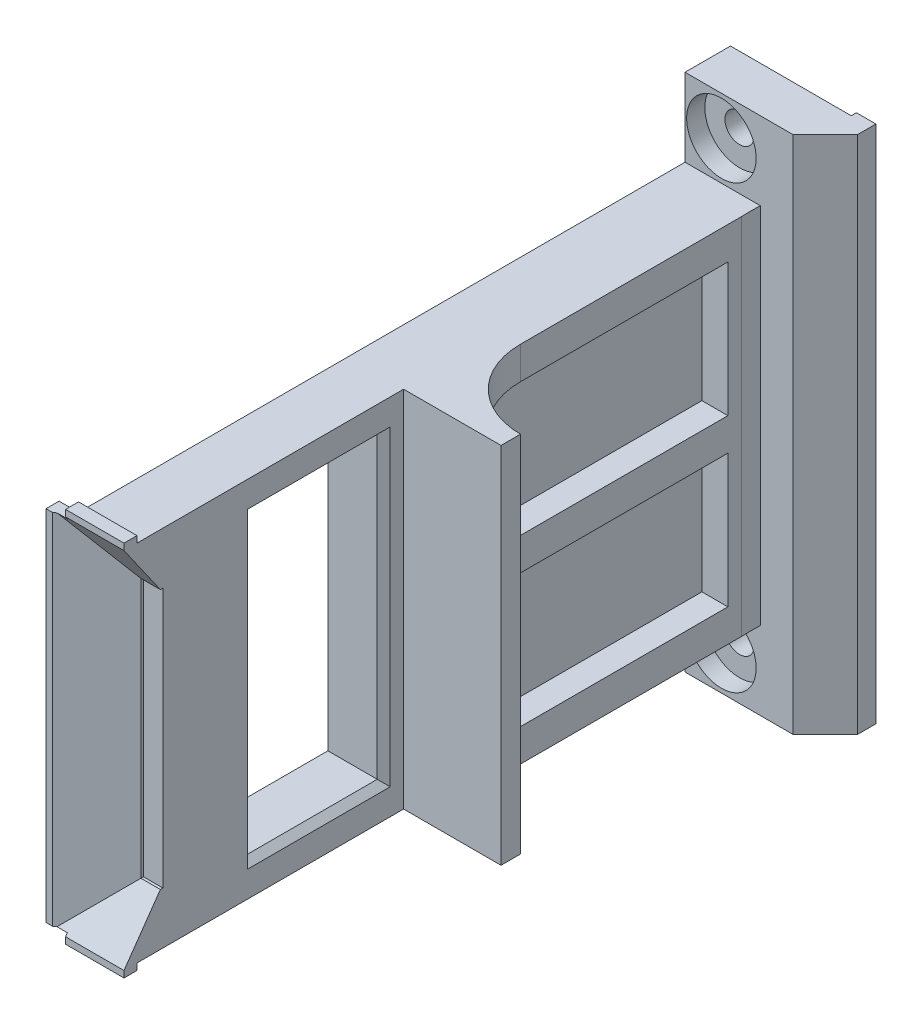
SolidWorks part; units mm, degrees
material "PLA"
ref_plane "정면" through (0, 0, 0) normal (0, 0, 1) x (1, 0, 0)
ref_plane "윗면" through (0, 0, 0) normal (0, 1, 0) x (1, 0, 0)
ref_plane "우측면" through (0, 0, 0) normal (1, 0, 0) x (0, 0, -1)
sketch "스케치1" plane through (0, 0, 0) normal (0, 0, 1) x (1, 0, 0)
  line L1 (-6, 23) -> (6, 23)
  line L2 (-6, 23) -> (-6, -23)
  line L3 (-6, -23) -> (6, -23)
  line L4 (6, 23) -> (6, -23)
  line L5 (-6, 23) -> (6, -23) construction
  line L6 (-6, -23) -> (6, 23) construction
  point P0 (0, 0)
  dimension "D1" = 46
  dimension "D2" = 12
extrude "보스-돌출1" add sketch "스케치1" along normal blind 59
sketch "스케치2" plane through (6, 0, 0) normal (1, 0, 0) x (0, 0, -1)
  line L0 (-59, -23) -> (-59, 23) construction
  line L1 (-42, 23.0809) -> (-22, 23.0809)
  line L2 (-42, 23.0809) -> (-42, -23)
  line L3 (-42, -23) -> (-22, -23)
  line L4 (-22, 23.0809) -> (-22, -23)
  line L6 (-59, -23) -> (0, -23) construction
  dimension "D1" = 17
  dimension "D2" = 20
extrude "컷-돌출1" cut sketch "스케치2" against normal blind 60
sketch "스케치3" plane through (0, -23, 0) normal (0, -1, 0) x (1, 0, 0)
  line L1 (6, 59) -> (-6, 59)
  line L2 (6, 59) -> (6, 0)
  line L3 (6, 0) -> (-6, 0)
  line L4 (-6, 59) -> (-6, 0)
extrude "보스-돌출2" add sketch "스케치3" along normal blind 5
ref_plane "평면1" through (0, 0, 0) normal (0, 1, 0) x (1, 0, 0)
mirror "대칭 복사1" about plane through (0, 0, 0) normal (0, 1, 0) of "보스-돌출2"
sketch "스케치4" plane through (0, 0, 0) normal (0, 0, -1) x (-1, 0, 0)
  line L1 (6, 28) -> (-6, 28)
  line L2 (6, 28) -> (6, -28)
  line L3 (6, -28) -> (-6, -28)
  line L4 (-6, 28) -> (-6, -28)
extrude "보스-돌출3" add sketch "스케치4" along normal blind 40
sketch "스케치5" plane through (0, -28, 0) normal (0, -1, 0) x (1, 0, 0)
  line L0 (6, -40) -> (6, 59) construction
  line L1 (-6, -40) -> (6, -40)
  line L2 (-6, -40) -> (-6, -33)
  line L3 (-6, -33) -> (6, -33)
  line L4 (6, -40) -> (6, -33)
  dimension "D1" = 7
extrude "보스-돌출4" add sketch "스케치5" along normal blind 12
mirror "대칭 복사2" about plane through (0, 0, 0) normal (0, 1, 0) of "보스-돌출4"
hole_wizard "M4 육각 머리 볼트용 카운터보어 (A 등급)1" positions "스케치6" profile "스케치7" counterbore size "M4" standard "KS" end condition through all
sketch "스케치6" plane through (0, 0, -33) normal (0, 0, 1) x (1, 0, 0)
  line L1 (-6, -40) -> (-6, -28) construction
  line L3 (6, -40) -> (6, -28) construction
  line L4 (6, 40) -> (-6, 40) construction
  line L6 (-6, 40) -> (-6, 28) construction
  point P0 (0, -34)
  point P2 (0, 34)
  point P18 (-6, -34)
  dimension "D1" = 0
  dimension "D2" = 6
  dimension "D3" = 6
  dimension "D4" = 6
sketch "스케치7" plane through (0, -34, -33) normal (1, 0, 0) x (0, -1, 0)
  line L0 (0, 0) -> (0, 7)
  line L1 (0, 7) -> (2.25, 7)
  line L3 (2.25, 7) -> (2.25, 2.8)
  line L4 (2.25, 2.8) -> (5.3525, 2.8)
  line L5 (5.3525, 2.8) -> (5.3525, 0)
  line L7 (5.3525, 0) -> (0, 0)
  line L11 (0, -6.35) -> (0, 107.95) construction
  dimension "관통 구멍 지름" = 4.5
  dimension "관통 구멍 깊이" = 7
  dimension "카운터보어 지름" = 10.705
  dimension "카운터보어 깊이" = 2.8
sketch "스케치8" plane through (0, 0, 59) normal (0, 0, 1) x (1, 0, 0)
  line L0 (6, 28) -> (-6, 28) construction
  line L1 (-9, -28) -> (6, -28)
  line L2 (-9, -28) -> (-9, 28)
  line L3 (-9, 28) -> (6, 28)
  line L4 (6, -28) -> (6, 28)
  dimension "D1" = 0
  dimension "D2" = 15
extrude "보스-돌출5" add sketch "스케치8" along normal blind 3
sketch "스케치9" plane through (0, 0, 62) normal (0, 0, 1) x (1, 0, 0)
  line L0 (6, -28) -> (6, 28) construction
  line L1 (6, -20) -> (0, -20)
  line L2 (6, -20) -> (6, 20)
  line L3 (6, 20) -> (0, 20)
  line L4 (0, -20) -> (0, 20)
  line L5 (6, 28) -> (-6, 28) construction
  line L6 (6, -28) -> (-6, -28) construction
  dimension "D1" = 8
  dimension "D2" = 8
  dimension "D3" = 6
extrude "컷-돌출2" cut sketch "스케치9" against normal blind 6
chamfer "모따기1" distance 8 angle 35 3 edges at (0, 0, 62) (3, 20, 62) (3, -20, 62)
sketch "스케치10" plane through (0, 0, -40) normal (0, 0, -1) x (-1, 0, 0)
  line L0 (-6, 40) -> (-6, -40) construction
  line L1 (-6, 19.6) -> (0, 19.6)
  line L2 (-6, 19.6) -> (-6, -19.6)
  line L3 (-6, -19.6) -> (0, -19.6)
  line L4 (0, 19.6) -> (0, -19.6)
  line L5 (6, 40) -> (-6, 40) construction
  line L6 (6, -40) -> (-6, -40) construction
  dimension "D1" = 20.4
  dimension "D2" = 6
  dimension "D3" = 20.4
extrude "보스-돌출6" add sketch "스케치10" along normal blind 9
sketch "스케치11" plane through (0, 0, 62) normal (0, 0, 1) x (1, 0, 0)
  line L0 (-6, 40) -> (-6, 28) construction
  line L1 (-9, 28) -> (-6, 28)
  line L2 (-9, 28) -> (-9, 27.6)
  line L3 (-9, 27.6) -> (-6, 27.6)
  line L4 (-6, 28) -> (-6, 27.6)
  line L5 (-9, -28) -> (-6, -28)
  line L6 (-9, -28) -> (-9, -27.6)
  line L7 (-9, -27.6) -> (-6, -27.6)
  line L8 (-6, -28) -> (-6, -27.6)
  line L9 (-6, -40) -> (-6, -28) construction
  dimension "D1" = 0
  dimension "D2" = 0.4
  dimension "D3" = 0.4
  dimension "D4" = 0
extrude "컷-돌출3" cut sketch "스케치11" against normal through all contours L7 L8 L5 L6 | L1 L4 L3 L2
chamfer "모따기2" distance 1 angle 45 2 edges at (-7.5, 27.6, 59) (-7.5, -27.6, 59)
chamfer "모따기3" distance 2 angle 35 4 edges at (0, 0, -49) (3, 19.6, -49) (3, -19.6, -49) (6, 0, -49)
sketch "스케치12" plane through (-6, 0, 0) normal (-1, 0, 0) x (0, 0, 1)
  line L0 (22, -23) -> (22, 23) construction
  line L1 (17, 23) -> (-28, 23)
  line L2 (17, 23) -> (17, 2.5)
  line L3 (17, 2.5) -> (-28, 2.5)
  line L4 (-28, 23) -> (-28, 2.5)
  line L5 (62, 28) -> (-33, 28) construction
  line L7 (55, 0) -> (-55, 0) construction
  line L8 (-28, -23) -> (-28, -2.5)
  line L9 (17, -2.5) -> (-28, -2.5)
  line L10 (17, -23) -> (17, -2.5)
  line L11 (17, -23) -> (-28, -23)
  dimension "D1" = 45
  dimension "D2" = 5
  dimension "D3" = 5
  dimension "D4" = 2.5
extrude "컷-돌출4" cut sketch "스케치12" against normal blind 4
ref_plane "평면2" through (0, 0, 0) normal (-1, 0, 0) x (0, 0, 1)
mirror "대칭 복사3" about plane through (0, 0, 0) normal (-1, 0, 0) of "컷-돌출4"
sketch "스케치14" plane through (6, 0, 0) normal (1, 0, 0) x (0, 0, -1)
  line L1 (33, 40) -> (40, 40)
  line L2 (33, 40) -> (33, -40)
  line L3 (33, -40) -> (40, -40)
  line L4 (40, 40) -> (40, -40)
extrude "보스-돌출7" add sketch "스케치14" along normal blind 10
sketch "스케치15" plane through (0, -40, 0) normal (0, -1, 0) x (1, 0, 0)
  line L0 (6, -33) -> (16, -33)
  line L1 (16, -33) -> (16, -28.3539)
  line L3 (16, -33) -> (16, -40) construction
  spline S0 degree 3 poles (6, -33) (5.5793, -24.0055) (9.5428, -28.1814) (15.1454, -28.3539) (16, -28.3539) knots 0 0 0 0 0.752788 1 1 1 1
extrude "컷-돌출5" cut sketch "스케치15" against normal through all
sketch "스케치16" plane through (6, 0, 0) normal (1, 0, 0) x (0, 0, -1)
  line L0 (30.1213, 28) -> (-62, 28) construction
  line L1 (-15.9394, 28) -> (-18.9394, 28)
  line L2 (-15.9394, 28) -> (-15.9394, -28)
  line L3 (-15.9394, -28) -> (-18.9394, -28)
  line L4 (-18.9394, 28) -> (-18.9394, -28)
  line L5 (30.1213, -28) -> (-62, -28) construction
  dimension "D1" = 3
extrude "보스-돌출8" add sketch "스케치16" along normal blind 12
chamfer "모따기5" distance 5 angle 45 1 edges at (16, 0, -33)
sketch "스케치17" plane through (0, 0, 62) normal (0, 0, 1) x (1, 0, 0)
  line L0 (-6, -28) -> (6, -28) construction
  line L1 (6, 28) -> (3, 28)
  line L2 (6, 28) -> (6, -28)
  line L3 (6, -28) -> (3, -28)
  line L4 (3, 28) -> (3, -28)
  dimension "D1" = 3
extrude "컷-돌출6" cut sketch "스케치17" against normal up to vertex
chamfer "모따기4" distance 1 angle 45 4 edges at (3, 23, 32) (3, 0, 42) (3, -23, 32) (3, 0, 22)
fillet "필렛1" radius 12 5 edges at (6, -25.5, 15.9394) (6, 0, 15.9394) (6, 25.5, 15.9394) (12, -28, 15.9394) (12, 28, 15.9394)
sketch "스케치22" plane through (0, 0, -40) normal (0, 0, -1) x (-1, 0, 0)
  line L0 (6, -40) -> (-16, -40) construction
  line L1 (-16, 40) -> (-13, 40)
  line L2 (-16, 40) -> (-16, -40)
  line L3 (-16, -40) -> (-13, -40)
  line L4 (-13, 40) -> (-13, -40)
  dimension "D1" = 3
extrude "보스-돌출11" add sketch "스케치22" along normal blind 0.8
sketch "스케치24" plane through (0, 28, 0) normal (0, 1, 0) x (1, 0, 0)
  line L1 (3, -62) -> (-6, -62)
  line L2 (3, -62) -> (3, -60)
  line L3 (3, -60) -> (-6, -60)
  line L4 (-6, -62) -> (-6, -60)
extrude "보스-돌출13" add sketch "스케치24" along normal blind 1
mirror "대칭 복사4" about plane through (0, 0, 0) normal (0, 1, 0) of "보스-돌출13"
sketch "스케치26" plane through (-6, 0, 0) normal (-1, 0, 0) x (0, 0, 1)
  line L0 (59, -26.6) -> (59, 26.6) construction
  line L1 (-40, 40) -> (59, 40)
  line L2 (-40, 40) -> (-40, -40)
  line L3 (-40, -40) -> (59, -40)
  line L4 (59, 40) -> (59, -40)
  point P5 (-40, -40)
extrude "컷-돌출8" cut sketch "스케치26" against normal blind 0.4
